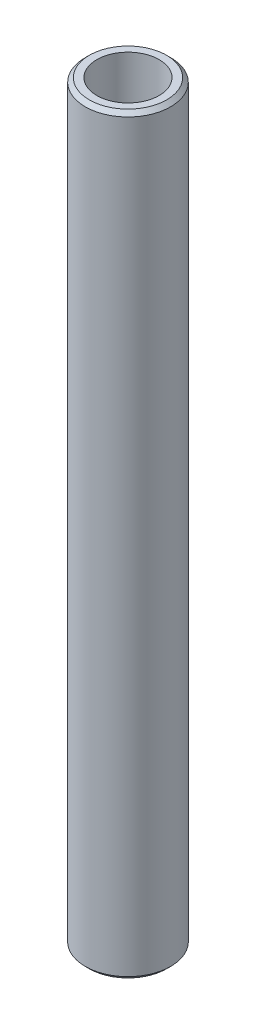
SolidWorks part; units mm, degrees
ref_plane "Front Plane" through (0, 0, 0) normal (0, 0, 1) x (1, 0, 0)
ref_plane "Top Plane" through (0, 0, 0) normal (0, 1, 0) x (1, 0, 0)
ref_plane "Right Plane" through (0, 0, 0) normal (1, 0, 0) x (0, 0, -1)
sketch "Sketch1" plane through (0, 0, 0) normal (0, 1, 0) x (1, 0, 0)
  circle A0 centre (0, 0) radius 17.5
  dimension "SHAFT_OD" = 35
extrude "Boss-Extrude1" add sketch "Sketch1" along normal blind 308.6296
sketch "Sketch2" plane through (0, 0, 0) normal (0, 1, 0) x (1, 0, 0)
  circle A0 centre (0, 0) radius 12.7795
  dimension "BORE_D" = 25.559
extrude "Cut-Extrude1" cut sketch "Sketch2" along normal through all
chamfer "Chamfer1" distance 1.6409 angle 45 2 edges at (0, 308.6296, 17.5) (0, 0, 17.5)
